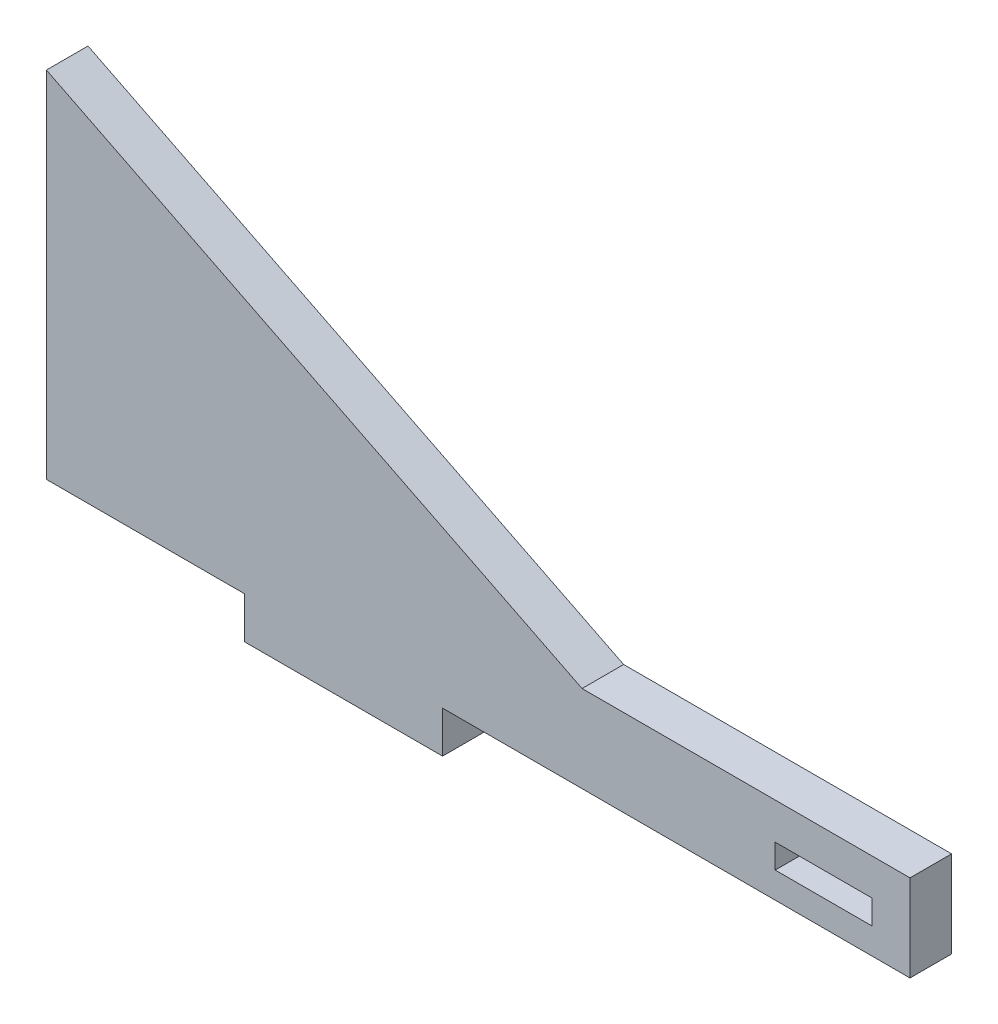
SolidWorks part; units mm, degrees
ref_plane "Front Plane" through (0, 0, 0) normal (0, 0, 1) x (1, 0, 0)
ref_plane "Top Plane" through (0, 0, 0) normal (0, 1, 0) x (1, 0, 0)
ref_plane "Right Plane" through (0, 0, 0) normal (1, 0, 0) x (0, 0, -1)
sketch "Sketch1" plane through (0, 0, 0) normal (0, 0, 1) x (1, 0, 0)
  line L0 (38.1, -20.066) -> (38.1, -12.7) construction
  line L1 (-38.1, -20.066) -> (-12.7, -20.066)
  line L2 (38.1, -12.7) -> (38.1, -20.066)
  line L3 (12.7, -25.4) -> (-12.7, -25.4)
  line L4 (-38.1, 25.4) -> (-38.1, -20.066)
  line L5 (5.4429, 3.6286) -> (-30.099, -20.066) construction
  line L6 (30.099, -20.066) -> (-38.1, 25.4) construction
  line L7 (-38.1, 25.4) -> (38.1, -12.7)
  line L9 (12.7, -20.066) -> (38.1, -20.066)
  line L10 (-12.7, -20.066) -> (-12.7, -25.4)
  line L11 (12.7, -20.066) -> (12.7, -25.4)
  point P0 (0, 0)
  dimension "D1" = 5.334
extrude "Boss-Extrude1" add sketch "Sketch1" along normal blind 5.334
sketch "Sketch2" plane through (0, 0, 5.334) normal (0, 0, 1) x (1, 0, 0)
  line L0 (38.1, -20.066) -> (72.644, -20.066)
  line L1 (72.644, -12.7) -> (72.644, -8.9443) construction
  line L2 (72.644, -20.066) -> (72.644, -12.7)
  line L3 (-38.1, -20.066) -> (72.644, -20.066) construction
  line L4 (72.644, -8.9443) -> (30.5885, -8.9443) construction
  line L5 (38.1, -12.7) -> (-38.1, 25.4) construction
  line L6 (30.5885, -8.9443) -> (72.644, -8.9443)
  line L7 (30.5885, -8.9443) -> (38.1, -12.7)
  line L8 (72.644, -12.7) -> (72.644, -8.9443)
  line L12 (-38.1, 25.4) -> (-38.1, -20.066)
  line L13 (-38.1, -20.066) -> (-12.7, -20.066)
  line L14 (-12.7, -20.066) -> (-12.7, -25.4)
  line L15 (-12.7, -25.4) -> (12.7, -25.4)
  line L16 (12.7, -25.4) -> (12.7, -20.066)
  line L17 (12.7, -20.066) -> (38.1, -20.066)
  line L18 (38.1, -20.066) -> (38.1, -12.7)
  line L19 (38.1, -12.7) -> (-38.1, 25.4)
  line L26 (38.1, -20.066) -> (38.1, -12.7)
  dimension "D1" = 110.744
  dimension "D2" = 0
extrude "Boss-Extrude2" add sketch "Sketch2" against normal through all
sketch "Sketch4" plane through (0, 0, 0) normal (0, 0, -1) x (-1, 0, 0)
  line L1 (-67.7758, -16.7235) -> (-55.3561, -16.7235)
  line L2 (-67.7758, -16.7235) -> (-67.7758, -13.6212)
  line L3 (-67.7758, -13.6212) -> (-55.3561, -13.6212)
  line L4 (-55.3561, -16.7235) -> (-55.3561, -13.6212)
  line L5 (-55.3561, -15.1724) -> (-72.644, -15.1724) construction
  line L6 (-72.644, -20.066) -> (-72.644, -8.9443) construction
extrude "Cut-Extrude1" cut sketch "Sketch4" against normal through all
equation "\"D1@Sketch1\" = \"Material\""
equation "\"Material\"= \"GMaterial@Platform.assembly\""
equation "\"D1@Boss-Extrude1\" = \"Material\""
